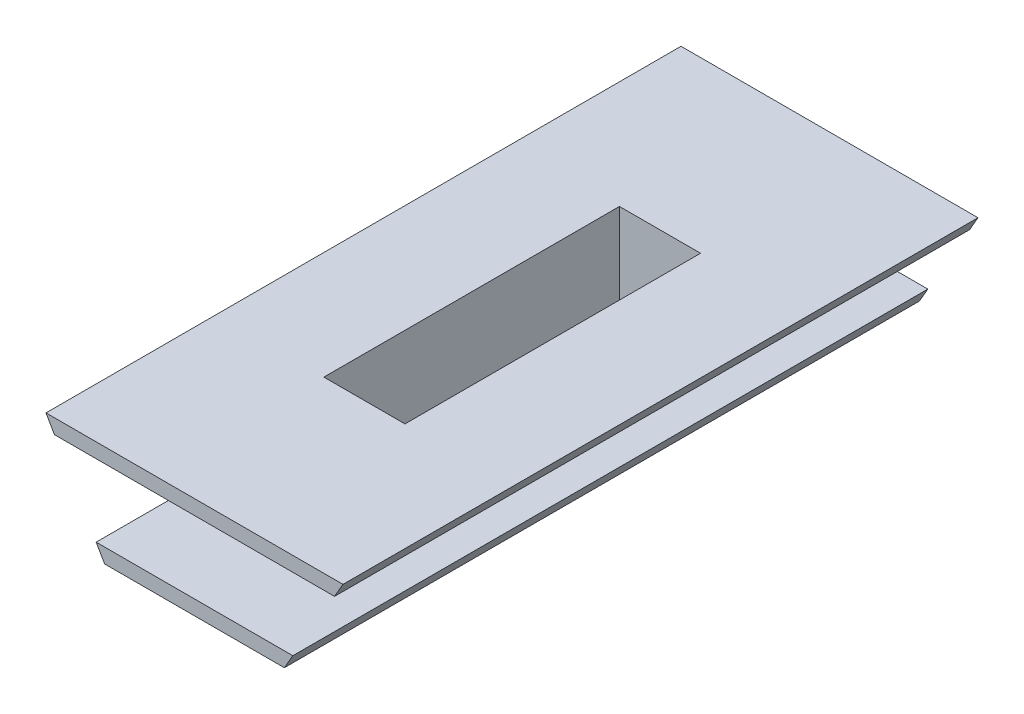
SolidWorks part; units mm, degrees
ref_plane "Front Plane" through (0, 0, 0) normal (0, 0, 1) x (1, 0, 0)
ref_plane "Top Plane" through (0, 0, 0) normal (0, 1, 0) x (1, 0, 0)
ref_plane "Right Plane" through (0, 0, 0) normal (1, 0, 0) x (0, 0, -1)
sketch "Casing" plane through (0, 0, 0) normal (0, 0, 1) x (1, 0, 0)
  line L0 (9.2, 0) -> (-9.2, 0)
  line L2 (0, 1.5) -> (0, 5.1962) construction
  line L4 (-9.2, 0) -> (-10.066, 1.5)
  line L5 (-15.2, 10.3923) -> (15.2, 10.3923)
  line L8 (9.2, 0) -> (10.066, 1.5)
  line L10 (-12.6019, 8.8923) -> (-5.15, 8.8923)
  line L12 (8.334, 1.5) -> (5.15, 1.5)
  line L14 (-14.334, 8.8923) -> (-5.15, 8.8923)
  line L16 (-10.066, 1.5) -> (-5.15, 1.5)
  line L17 (-14.334, 8.8923) -> (-15.2, 10.3923)
  line L18 (-9.2, 0) -> (-15.2, 10.3923) construction
  line L19 (14.334, 8.8923) -> (15.2, 10.3923)
  line L20 (9.2, 0) -> (15.2, 10.3923) construction
  line L21 (0, 5.1962) -> (-4.15, 5.1962) construction
  line L22 (-4.15, 8.8923) -> (-4.15, 1.5)
  line L23 (4.15, 8.8923) -> (4.15, 1.5)
  line L24 (-5.15, 8.8923) -> (-5.15, 1.5)
  line L25 (5.15, 8.8923) -> (5.15, 1.5)
  line L26 (-8.334, 1.5) -> (-12.6019, 8.8923) construction
  line L27 (8.334, 1.5) -> (12.6019, 8.8923) construction
  line L28 (4.15, 1.5) -> (-4.15, 1.5)
  line L29 (8.334, 1.5) -> (-8.334, 1.5) construction
  line L30 (5.15, 1.5) -> (10.066, 1.5)
  line L31 (5.15, 8.8923) -> (12.6019, 8.8923)
  line L32 (-12.6019, 8.8923) -> (12.6019, 8.8923) construction
  line L33 (5.15, 8.8923) -> (14.334, 8.8923)
  line L34 (-4.15, 1.5) -> (4.15, 1.5)
  line L35 (-5.15, 1.5) -> (-8.334, 1.5)
  line L36 (-4.15, 8.8923) -> (4.15, 8.8923)
  line L37 (-4.15, 8.8923) -> (4.15, 8.8923)
  line L38 (-12.6019, 8.8923) -> (-14.334, 8.8923)
  line L40 (12.6019, 8.8923) -> (14.334, 8.8923)
  line L41 (8.334, 1.5) -> (10.066, 1.5)
  point P8 (0, 10.3923)
  point P15 (0, 8.8923)
  point P18 (0, 1.5)
  point P22 (-4.15, 5.1962)
  dimension "D1" = 15.2
  dimension "D3" = 120
  dimension "D5" = 4.15
  dimension "D6" = 1
  dimension "D7" = 1
  dimension "D4" = 1.5
extrude "Boss-Extrude2" add sketch "Casing" along normal blind 65 contours L31 L33 L19 L5 L17 L14 L10 L24 L16 L4 L0 L8 L30 L12 L25 L22 L36 L23 L28 | L36 L22 L28 L23 region at (0, 0.3213, 0) region at (0, 5.1962, 0)
sketch "Sketch10" plane through (0, 0, 65) normal (0, 0, 1) x (1, 0, 0)
  line L0 (-5.15, 1.5) -> (5.15, 1.5)
  line L1 (-5.15, 1.5) -> (-5.15, 8.8924)
  line L2 (5.15, 1.5) -> (5.15, 8.8924)
  line L3 (-5.15, 8.8924) -> (5.15, 8.8924)
extrude "Top_Cut" cut sketch "Sketch10" against normal blind 16.35
sketch "Sketch11" plane through (0, 0, 0) normal (0, 0, -1) x (-1, 0, 0)
  line L0 (-5.15, 1.5) -> (5.15, 1.5)
  line L1 (-5.15, 1.5) -> (-5.15, 8.9052)
  line L2 (5.15, 1.5) -> (5.15, 8.9052)
  line L3 (-5.15, 8.9052) -> (5.15, 8.9052)
extrude "Bot_Cut" cut sketch "Sketch11" against normal blind 16.35
sketch "Sketch13" plane through (0, 10.3923, 0) normal (0, 1, 0) x (1, 0, 0)
  line L0 (-5.15, -16.35) -> (5.15, -16.35)
  line L1 (-5.15, -16.35) -> (-5.15, -48.6057)
  line L2 (5.15, -16.35) -> (5.15, -48.6057)
  line L3 (-5.15, -48.6057) -> (5.15, -48.6057)
  line L4 (-4.15, -17.35) -> (4.15, -17.35)
  line L5 (4.15, -17.35) -> (4.15, -47.6057)
  line L6 (-4.15, -47.6057) -> (4.15, -47.6057)
  line L7 (-4.15, -17.35) -> (-4.15, -47.6057)
  dimension "D1" = 1
extrude "Cut-Extrude8" cut sketch "Sketch13" against normal through all contours L4 L5 L6 L7
fillet "Fillet1" radius 1 4 edges at (-5.15, 5.1962, 48.65) (5.15, 5.1962, 48.65) (-5.15, 5.1962, 16.35) (5.15, 5.1962, 16.35)
